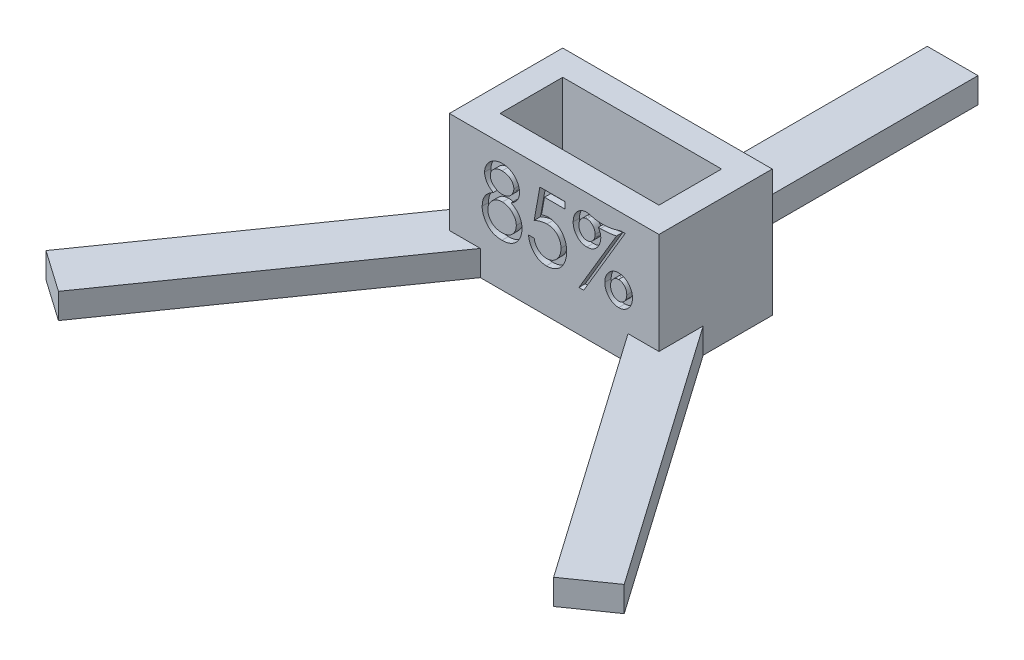
SolidWorks part; units mm, degrees
ref_plane "Front Plane" through (0, 0, 0) normal (0, 0, 1) x (1, 0, 0)
ref_plane "Top Plane" through (0, 0, 0) normal (0, 1, 0) x (1, 0, 0)
ref_plane "Right Plane" through (0, 0, 0) normal (1, 0, 0) x (0, 0, -1)
sketch "Sketch1" plane through (0, 0, 0) normal (0, 1, 0) x (1, 0, 0)
  line L0 (-16.5349, 8.9403) -> (16.5349, 8.9403)
  line L1 (-12.5349, -4.9403) -> (12.5349, -4.9403)
  line L2 (-12.5349, -4.9403) -> (-12.5349, 4.9403)
  line L3 (-12.5349, 4.9403) -> (12.5349, 4.9403)
  line L4 (12.5349, -4.9403) -> (12.5349, 4.9403)
  line L5 (-12.5349, -4.9403) -> (12.5349, 4.9403) construction
  line L6 (-12.5349, 4.9403) -> (12.5349, -4.9403) construction
  line L7 (16.5349, -8.9403) -> (16.5349, 8.9403)
  line L8 (-16.5349, -8.9403) -> (16.5349, -8.9403)
  line L9 (-16.5349, -8.9403) -> (-16.5349, 8.9403)
  line L10 (-16.5349, -8.9403) -> (-42.3458, -45.8021) construction
  line L11 (4, 8.9403) -> (4, 53.9403)
  line L12 (42.3458, -45.8021) -> (16.5349, -8.9403) construction
  line L13 (0, 8.9403) -> (0, 53.9403) construction
  line L14 (-16.5349, -1.9665) -> (-45.6224, -43.5078)
  line L15 (45.6224, -43.5078) -> (16.5349, -1.9665)
  line L16 (-4, 8.9403) -> (-4, 53.9403)
  line L17 (-11.6518, -8.9403) -> (-39.0692, -48.0964)
  line L18 (39.0692, -48.0964) -> (11.6518, -8.9403)
  line L19 (4, 8.9403) -> (-4, 8.9403)
  line L20 (4, 53.9403) -> (-4, 53.9403)
  line L21 (-19.8115, -6.646) -> (-13.2583, -11.2346) construction
  line L22 (-45.6224, -43.5078) -> (-39.0692, -48.0964)
  line L23 (45.6224, -43.5078) -> (39.0692, -48.0964)
  line L24 (19.8115, -6.646) -> (13.2583, -11.2346) construction
  line L25 (-19.8115, -6.646) -> (-45.6224, -43.5078) construction
  line L26 (-13.2583, -11.2346) -> (-39.0692, -48.0964) construction
  line L27 (39.0692, -48.0964) -> (13.2583, -11.2346) construction
  line L28 (45.6224, -43.5078) -> (19.8115, -6.646) construction
  point P0 (0, 0)
  dimension "D1" = 9.8806
  dimension "D2" = 25.0698
  dimension "D4" = 125
  dimension "D5" = 125
  dimension "D6" = 45
  dimension "D3" = 4
  dimension "D7" = 4
  dimension "D8" = 4
extrude "Boss-Extrude1" add sketch "Sketch1" along normal blind 4 contours L14 L22 L17 L8 L9 | L11 L20 L16 L0 | L23 L15 L7 L8 L18 region at (0, 0, -31.4403) region at (-28.8502, 0, 26.4566) region at (28.8502, 0, 26.4566)
extrude "Boss-Extrude2" add sketch "Sketch1<3>" along normal blind 20 contours L9 L8 L7 L0 L4 L1 L2 L3 region at (-10.2675, 0, -8.5644)
sketch "Sketch1<3>" plane through (0, 0, 0) normal (0, 1, 0) x (1, 0, 0) same geometry as "Sketch1"
sketch "Sketch2" plane through (0, 0, 8.9403) normal (0, 0, 1) x (1, 0, 0)
  text T0 "85%" font "Century Gothic" height 10
extrude "Cut-Extrude1" cut sketch "Sketch2" against normal blind 1
